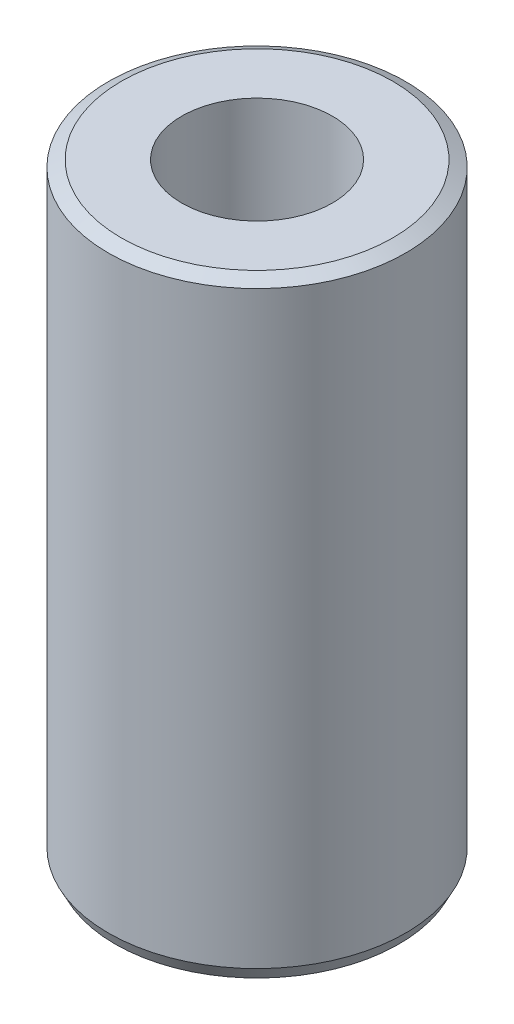
SolidWorks part; units mm, degrees
ref_plane "Front Plane" through (0, 0, 0) normal (0, 0, 1) x (1, 0, 0)
ref_plane "Top Plane" through (0, 0, 0) normal (0, 1, 0) x (1, 0, 0)
ref_plane "Right Plane" through (0, 0, 0) normal (1, 0, 0) x (0, 0, -1)
sketch "Sketch1" plane through (0, 0, 0) normal (0, 1, 0) x (1, 0, 0)
  circle A0 centre (0, 0) radius 50
  dimension "SHAFT_OD" = 100
extrude "Boss-Extrude1" add sketch "Sketch1" along normal blind 204.7169
sketch "Sketch2" plane through (0, 0, 0) normal (0, 1, 0) x (1, 0, 0)
  circle A0 centre (0, 0) radius 25.355
  dimension "BORE_D" = 50.7099
extrude "Cut-Extrude1" cut sketch "Sketch2" along normal through all
chamfer "Chamfer1" distance 2.2402 angle 62.672 2 edges at (0, 204.7169, 50) (0, 0, 50) first distance on face at (0, 204.7169, 50) first distance on face at (0, 0, 25.355)
